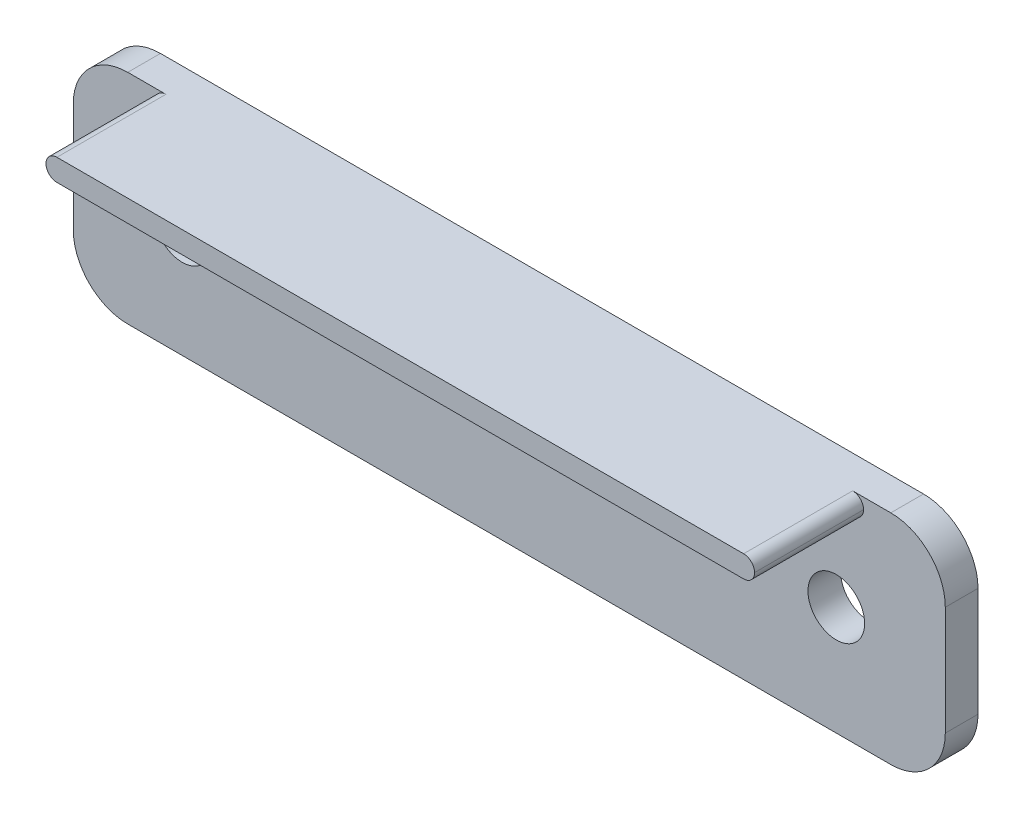
SolidWorks part; units mm, degrees
ref_plane "正面" through (0, 0, 0) normal (0, 0, 1) x (1, 0, 0)
ref_plane "平面" through (0, 0, 0) normal (0, 1, 0) x (1, 0, 0)
ref_plane "右側面" through (0, 0, 0) normal (1, 0, 0) x (0, 0, -1)
sketch "ｽｹｯﾁ2" plane through (0, 0, 0) normal (0, 0, 1) x (1, 0, 0)
  line L0 (-30, 0) -> (30, 0) construction
  line L2 (-40, -10) -> (40, -10)
  line L3 (-40, -10) -> (-40, 10)
  line L4 (-40, 10) -> (40, 10)
  line L5 (40, -10) -> (40, 10)
  line L6 (-40, -10) -> (40, 10) construction
  line L7 (-40, 10) -> (40, -10) construction
  circle A0 centre (-30, 0) radius 2.6
  circle A1 centre (30, 0) radius 2.6
  circle A2 centre (0, 0) radius 2.6 construction
  point P4 (0, 0)
  point P7 (0, 0)
  dimension "D1" = 5.2
  dimension "D4" = 10
  dimension "D2" = 60
  dimension "D3" = 20
extrude "ﾎﾞｽ - 押し出し1" add sketch "ｽｹｯﾁ2" along normal blind 3
sketch "ｽｹｯﾁ3" plane through (0, 0, 3) normal (0, 0, 1) x (1, 0, 0)
  line L0 (0, -10) -> (0, 10) construction
  line L1 (-40, -10) -> (40, -10) construction
  line L2 (40, 10) -> (-40, 10) construction
  line L4 (32.5, 8) -> (-32.5, 8)
  line L5 (32.5, 8) -> (32.5, 10)
  line L6 (32.5, 10) -> (-32.5, 10)
  line L7 (-32.5, 8) -> (-32.5, 10)
  line L8 (32.5, 8) -> (-32.5, 10) construction
  line L9 (32.5, 10) -> (-32.5, 8) construction
  point P6 (0, 9)
  dimension "D1" = 2
  dimension "D2" = 65
extrude "ﾎﾞｽ - 押し出し2" add sketch "ｽｹｯﾁ3" along normal blind 10
fillet "ﾌｨﾚｯﾄ1" radius 1 4 edges at (-32.5, 10, 8) (-32.5, 8, 8) (32.5, 10, 8) (32.5, 8, 8)
fillet "ﾌｨﾚｯﾄ2" radius 5 4 edges at (-40, -10, 1.5) (-40, 10, 1.5) (40, -10, 1.5) (40, 10, 1.5)
